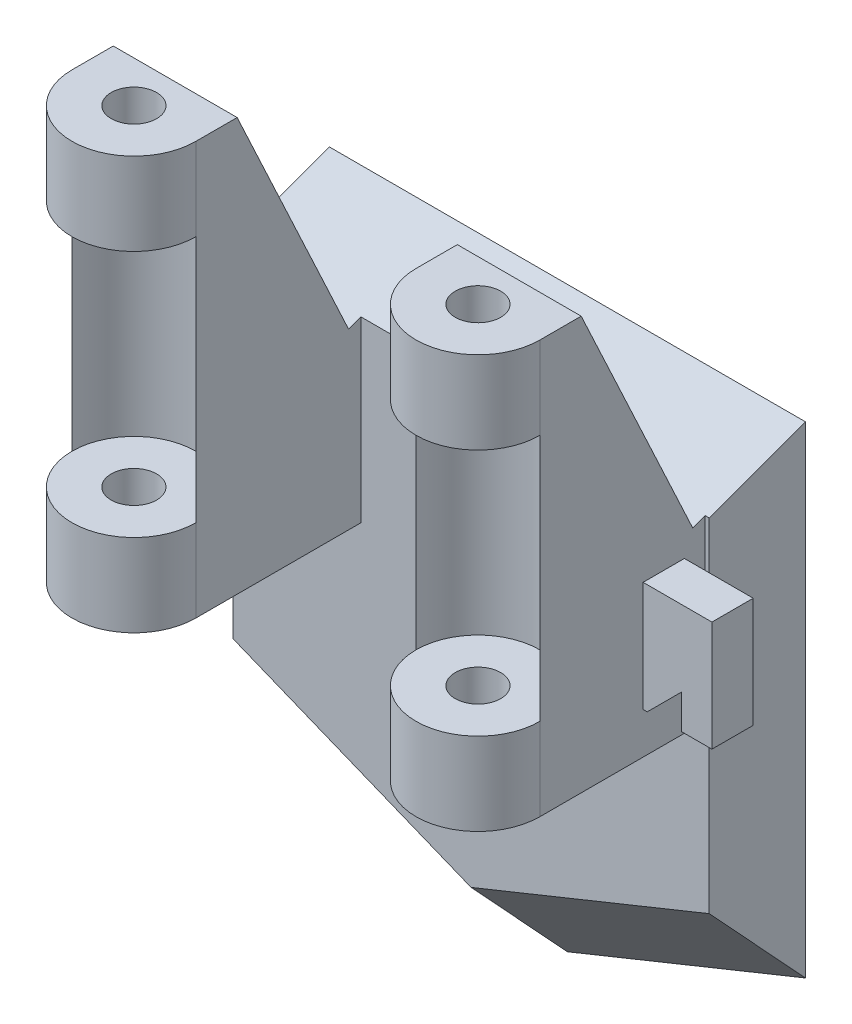
SolidWorks part; units mm, degrees
ref_plane "Plano frontal" through (0, 0, 0) normal (0, 0, 1) x (1, 0, 0)
ref_plane "Plano superior" through (0, 0, 0) normal (0, 1, 0) x (1, 0, 0)
ref_plane "Plano direito" through (0, 0, 0) normal (1, 0, 0) x (0, 0, -1)
sketch "Esboço1" plane through (0, 0, 0) normal (0, 0, 1) x (1, 0, 0)
  line L1 (-17.3, 13) -> (17.3, 13)
  line L2 (-17.3, 13) -> (-17.3, -13)
  line L3 (-17.3, -13) -> (17.3, -13)
  line L4 (17.3, 13) -> (17.3, -13)
  line L5 (-17.3, 13) -> (17.3, -13) construction
  line L6 (-17.3, -13) -> (17.3, 13) construction
  point P0 (0, 0)
  dimension "D1" = 34.6
  dimension "D2" = 26
extrude "Ressalto-extrusão1" add sketch "Esboço1" along normal blind 7
sketch "Esboço10" plane through (0, 0, 0) normal (0, 0, -1) x (-1, 0, 0)
  line L0 (-17.3, -19.5) -> (0, -26.5)
  line L1 (-17.3, 13) -> (17.3, 13)
  line L2 (-17.3, 13) -> (-17.3, 15.5)
  line L3 (-17.3, 15.5) -> (17.3, 15.5)
  line L4 (17.3, 13) -> (17.3, 15.5)
  line L5 (0, -26.5) -> (17.3, -19.5)
  line L6 (-17.3, -19.5) -> (-17.3, -13)
  line L7 (-17.3, -13) -> (17.3, -13)
  line L8 (17.3, -13) -> (17.3, -19.5)
  dimension "D1" = 7
  dimension "D2" = 35
  dimension "D3" = 2.5
extrude "Ressalto-extrusão4" add sketch "Esboço10" against normal up to surface (7 mm away) up to face at (0, 0, 7)
chamfer "Chanfro1" distance 7 angle 45 2 edges at (8.65, -23, 7) (-8.65, -23, 7)
chamfer "Chanfro2" distance 7 angle 20 1 edges at (0, 15.5, 7) first distance on face at (0, 15.5, 3.5)
sketch "Esboço12" plane through (0, 0, 0) normal (0, 1, 0) x (1, 0, 0)
  line L0 (0, 0) -> (0, -11.8858) construction
  line L1 (-17, -19) -> (-17, -7)
  line L2 (-17.3, -7) -> (0, -7) construction
  line L3 (-17, -7) -> (-8, -7)
  line L4 (-8, -7) -> (-8, -19)
  line L5 (8, -7) -> (8, -19)
  line L6 (17, -7) -> (8, -7)
  line L7 (17, -19) -> (17, -7)
  arc A0 (-17, -19) -> (-8, -19) centre (-12.5, -19) ccw
  circle A1 centre (-12.5, -19) radius 1.65
  circle A2 centre (12.5, -19) radius 1.65
  arc A3 (17, -19) -> (8, -19) centre (12.5, -19) cw
  dimension "D2" = 3.3
  dimension "D4" = 4.5
  dimension "D3" = 12
  dimension "D5" = 25
extrude "Ressalto-extrusão5" add sketch "Esboço12" along normal blind 30
sketch "Esboço15" plane through (0, 0, 0) normal (0, 1, 0) x (1, 0, 0)
  line L0 (-22, -11.5) -> (-22, -8.5)
  line L1 (-22, -8.5) -> (-17, -8.5)
  line L2 (-17, -7) -> (-17, -19) construction
  line L3 (-17, -7) -> (-8, -7)
  line L4 (-8, -7) -> (-8, -11.5)
  line L5 (-8, -19) -> (-8, -7) construction
  line L6 (-22, -11.5) -> (-8, -11.5)
  line L7 (-17, -8.5) -> (-17, -7)
  line L8 (0, 0) -> (0, -17.602) construction
  line L9 (17, -8.5) -> (17, -7)
  line L10 (22, -11.5) -> (8, -11.5)
  line L11 (8, -7) -> (8, -11.5)
  line L12 (17, -7) -> (8, -7)
  line L13 (22, -8.5) -> (17, -8.5)
  line L14 (22, -11.5) -> (22, -8.5)
  dimension "D1" = 1.5
  dimension "D2" = 5
  dimension "D3" = 3
extrude "Ressalto-extrusão6" add sketch "Esboço15" along normal blind 8 from offset 3
sketch "Esboço16" plane through (0, 0, 11.5) normal (0, 0, 1) x (1, 0, 0)
  line L0 (-17.3, 3) -> (-19.8, 5.5)
  line L1 (-17.3, 12.9522) -> (-17.3, -11.9487) construction
  line L2 (-22, 3) -> (-17, 3) construction
  line L3 (-19.8, 5.5) -> (-19.8, 3)
  line L4 (-19.8, 3) -> (-17.3, 3)
  line L5 (0, 0) -> (0, -5.9818) construction
  line L6 (19.8, 3) -> (17.3, 3)
  line L7 (19.8, 5.5) -> (19.8, 3)
  line L8 (17.3, 3) -> (19.8, 5.5)
  dimension "D1" = 2.5
  dimension "D2" = 2.5
extrude "Corte-extrusão2" cut sketch "Esboço16" against normal through all both and the other way through all
chamfer "Chanfro3" distance 9 angle 65 2 edges at (-12.5, 30, 7) (12.5, 30, 7) first distance on face at (-12.5, 21.4761, 7) first distance on face at (12.5, 30, 14.125)
sketch "Esboço17" plane through (0, 0, 0) normal (0, -1, 0) x (1, 0, 0)
  circle A0 centre (-12.5, 19) radius 4.5
  circle A1 centre (12.5, 19) radius 4.5
  arc A2 (17, 19) -> (8, 19) centre (12.5, 19) ccw construction
  arc A3 (-8, 19) -> (-17, 19) centre (-12.5, 19) ccw construction
extrude "Corte-extrusão3" cut sketch "Esboço17" against normal offset from surface (18 mm away) 6 from offset 6 up to face at (-12.5, 30, 18.625) offset against normal yes
